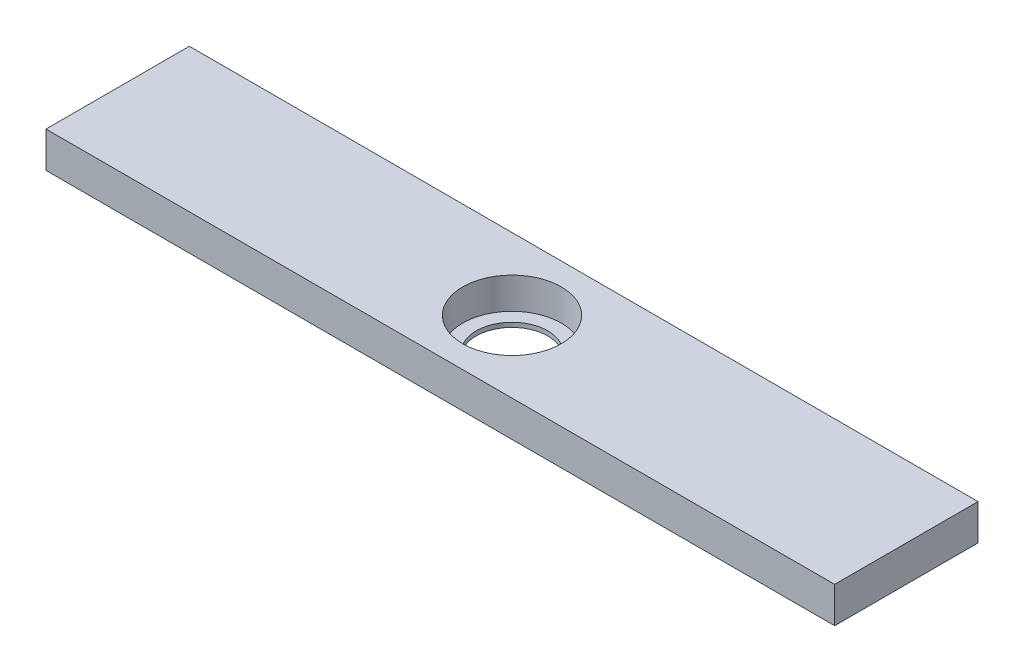
SolidWorks part; units mm, degrees
ref_plane "Front Plane" through (0, 0, 0) normal (0, 0, 1) x (1, 0, 0)
ref_plane "Top Plane" through (0, 0, 0) normal (0, 1, 0) x (1, 0, 0)
ref_plane "Right Plane" through (0, 0, 0) normal (1, 0, 0) x (0, 0, -1)
sketch "Sketch1" plane through (0, 0, 0) normal (0, 1, 0) x (1, 0, 0)
  line L1 (-139.7, -25.4) -> (139.7, -25.4)
  line L2 (-139.7, -25.4) -> (-139.7, 25.4)
  line L3 (-139.7, 25.4) -> (139.7, 25.4)
  line L4 (139.7, -25.4) -> (139.7, 25.4)
  line L5 (-139.7, -25.4) -> (139.7, 25.4) construction
  line L6 (-139.7, 25.4) -> (139.7, -25.4) construction
  point P0 (0, 0)
  dimension "D1" = 279.4
  dimension "D2" = 50.8
extrude "Boss-Extrude1" add sketch "Sketch1" along normal blind 12.7
sketch "Sketch2" plane through (0, 12.7, 0) normal (0, 1, 0) x (1, 0, 0)
  circle A0 centre (0, 0) radius 17.4625
  dimension "D1" = 34.925
extrude "Cut-Extrude1" cut sketch "Sketch2" against normal blind 11.1125
sketch "Sketch3" plane through (0, 1.5875, 0) normal (0, 1, 0) x (1, 0, 0)
  circle A0 centre (0, 0) radius 12.7
  dimension "D1" = 25.4
extrude "Cut-Extrude2" cut sketch "Sketch3" against normal through all
